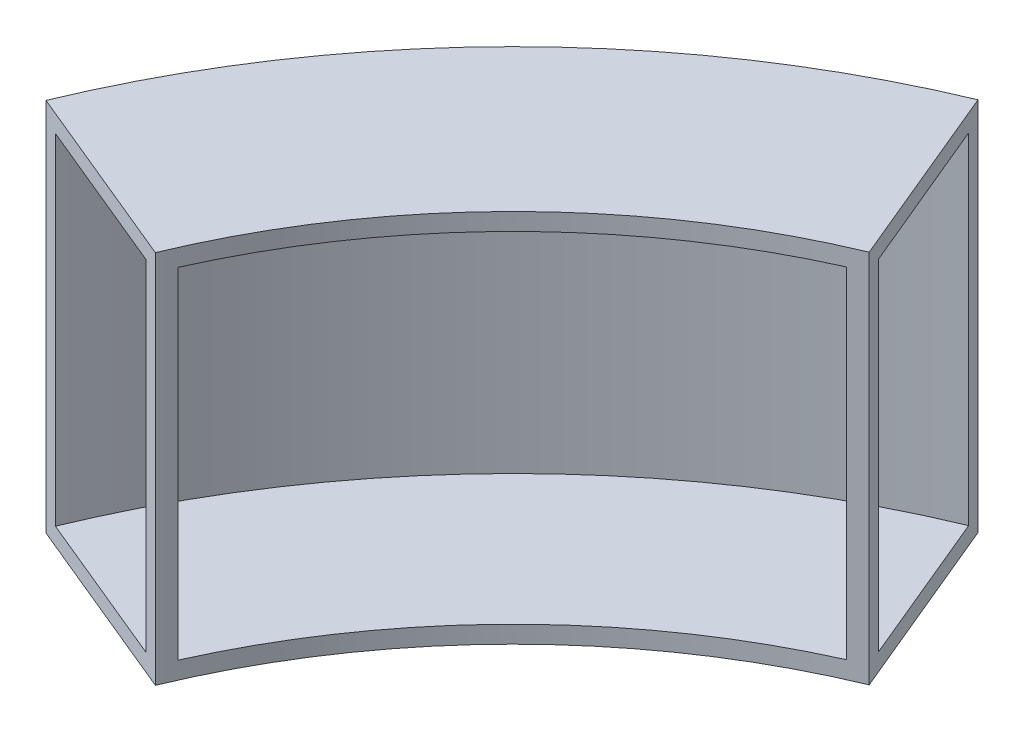
SolidWorks part; units mm, degrees
material "Alumina"
ref_plane "Front Plane" through (0, 0, 0) normal (0, 0, 1) x (1, 0, 0)
ref_plane "Top Plane" through (0, 0, 0) normal (0, 1, 0) x (1, 0, 0)
ref_plane "Right Plane" through (0, 0, 0) normal (1, 0, 0) x (0, 0, -1)
sketch "Sketch1" plane through (0, 0, 0) normal (0, 1, 0) x (1, 0, 0)
  line L0 (0, 1495.54) -> (0, -1495.54) construction
  line L1 (0, 0) -> (1057.5065, 1057.5065) construction
  line L2 (1057.5065, 1057.5065) -> (-1057.5065, -1057.5065) construction
  line L3 (-1057.5065, -1057.5065) -> (1057.5065, -1057.5065) construction
  line L4 (1057.5065, -1057.5065) -> (-1057.5065, 1057.5065) construction
  line L5 (-1057.5065, 1057.5065) -> (1057.5065, 1057.5065) construction
  line L6 (440.104, -1057.5065) -> (574.625, -1380.7411)
  line L7 (440.104, 1057.5065) -> (574.625, 1380.7411)
  line L8 (-440.104, 1057.5065) -> (-574.625, 1380.7411)
  line L9 (-440.104, -1057.5065) -> (-574.625, -1380.7411)
  line L10 (-1058.4838, 437.7482) -> (-1382.0172, 571.5491)
  circle A0 centre (0, 0) radius 1495.54
  arc A2 (440.104, 1057.5065) -> (440.104, -1057.5065) centre (0, 0) cw
  arc A3 (-440.104, -1057.5065) -> (-440.104, 1057.5065) centre (0, 0) cw
  arc A4 (-440.104, 1057.5065) -> (-1058.4838, 437.7482) centre (0, 0) ccw
extrude "Boss-Extrude1" add sketch "Sketch1" along normal blind 650 contours L10 A3 L8 A0 region at (-916.326, 0, -914.2879)
sketch "Sketch3" plane through (0, 0, 0) normal (-0.3822, 0, 0.9241) x (0.9241, 0, 0.3822)
  line L0 (-1145.4307, 0) -> (-1495.54, 650) construction
  line L1 (-1495.54, 0) -> (-1145.4307, 650) construction
  line L2 (-1145.4307, 650) -> (-1175.4307, 650) construction
  line L3 (-1145.4307, 650) -> (-1495.54, 650) construction
  line L4 (-1320.4853, 325) -> (-1320.4853, 650) construction
  line L5 (-1320.4853, 650) -> (-1320.4853, 0) construction
  line L6 (-1145.4307, 0) -> (-1495.54, 0) construction
  line L7 (-1495.54, 325) -> (-1145.4307, 325) construction
  line L8 (-1495.54, 650) -> (-1495.54, 0) construction
  line L9 (-1145.4307, 650) -> (-1145.4307, 0) construction
  line L10 (-1145.4307, 650) -> (-1145.4307, 620) construction
  line L11 (-1175.4307, 650) -> (-1175.4307, 620) construction
  line L12 (-1175.4307, 620) -> (-1145.4307, 620) construction
  line L13 (-1175.4307, 30) -> (-1145.4307, 30) construction
  line L14 (-1175.4307, 0) -> (-1175.4307, 30) construction
  line L15 (-1465.54, 620) -> (-1495.54, 620) construction
  line L16 (-1465.54, 30) -> (-1495.54, 30) construction
  line L17 (-1465.54, 0) -> (-1465.54, 30) construction
  line L18 (-1465.54, 650) -> (-1465.54, 620) construction
  line L19 (-1465.54, 620) -> (-1175.4307, 620)
  line L20 (-1175.4307, 620) -> (-1175.4307, 30)
  line L21 (-1175.4307, 30) -> (-1465.54, 30)
  line L22 (-1465.54, 30) -> (-1465.54, 620)
  line L23 (0, 0) -> (0, 1000.043) construction
revolve "Cut-Revolve1" cut sketch "Sketch3" angle 360 about L23
sketch "Sketch4" plane through (0, 0, 0) normal (-0.3822, 0, 0.9241) x (0.9241, 0, 0.3822)
  line L0 (-1175.4307, 620) -> (-1145.4307, 620)
  line L1 (-1145.4307, 650) -> (-1145.4307, 0) construction
  line L2 (-1175.4307, 30) -> (-1145.4307, 30)
  line L3 (-1145.4307, 30) -> (-1145.4307, 620)
  line L4 (-1175.4307, 620) -> (-1175.4307, 30)
  line L5 (0, 0) -> (0, 1002.6948) construction
revolve "Cut-Revolve2" cut sketch "Sketch4" about L5 reverse direction yes
sketch "Sketch5" plane through (0, 0, 0) normal (-0.3822, 0, 0.9241) x (0.9241, 0, 0.3822)
  line L2 (-1145.4307, 0) -> (-1495.54, 0) construction
  line L3 (0, 0) -> (0, 650) construction
  line L4 (-1145.4307, 650) -> (-1495.54, 650) construction
  line L6 (0, 0) -> (0, 587.3873) construction
  line L7 (-1145.4307, 620) -> (-1175.4307, 620)
  line L8 (-1145.4307, 620) -> (-1465.54, 620) construction
  line L9 (-1175.4307, 620) -> (-1175.4307, 30)
  line L10 (-1465.54, 30) -> (-1145.4307, 30) construction
  line L11 (-1175.4307, 30) -> (-1145.4307, 30)
  line L12 (-1145.4307, 30) -> (-1145.4307, 620)
sketch "Sketch7" plane through (0, 0, 0) normal (-0.3822, 0, 0.9241) x (0.9241, 0, 0.3822)
  line L0 (-1145.4307, 620) -> (-1145.4307, 30)
  line L1 (-1145.4307, 30) -> (-1175.4307, 30)
  line L2 (-1175.4307, 30) -> (-1175.4307, 620)
  line L3 (-1175.4307, 620) -> (-1145.4307, 620)
  line L4 (0, 0) -> (0, 650) construction
revolve "Revolve1" add sketch "Sketch7" angle 1.5 about L4 reverse direction yes
sketch "Sketch8" plane through (0, 0, 0) normal (0.9232, 0, -0.3842) x (-0.3842, 0, -0.9232)
  line L0 (1175.4307, 620) -> (1145.4307, 620)
  line L1 (1145.4307, 650) -> (1145.4307, 0) construction
  line L2 (1175.4307, 620) -> (1175.4307, 30)
  line L3 (1175.4307, 30) -> (1145.4307, 30)
  line L4 (1145.4307, 30) -> (1145.4307, 620)
  line L5 (0, 0) -> (0, 839.8381) construction
revolve "Cut-Revolve5" cut sketch "Sketch8" angle 2 about L5
sketch "Sketch9" plane through (0, 0, 0) normal (0.9232, 0, -0.3842) x (-0.3842, 0, -0.9232)
  line L7 (1145.4307, 620) -> (1175.4307, 620)
  line L8 (1145.4307, 620) -> (1465.54, 620) construction
  line L9 (1175.4307, 620) -> (1175.4307, 30)
  line L10 (1465.54, 30) -> (1145.4307, 30) construction
  line L11 (1175.4307, 30) -> (1145.4307, 30)
  line L12 (1145.4307, 30) -> (1145.4307, 620)
  line L13 (0, 0) -> (0, 807.4983) construction
revolve "Revolve2" add sketch "Sketch9" angle 1.5 about L13
